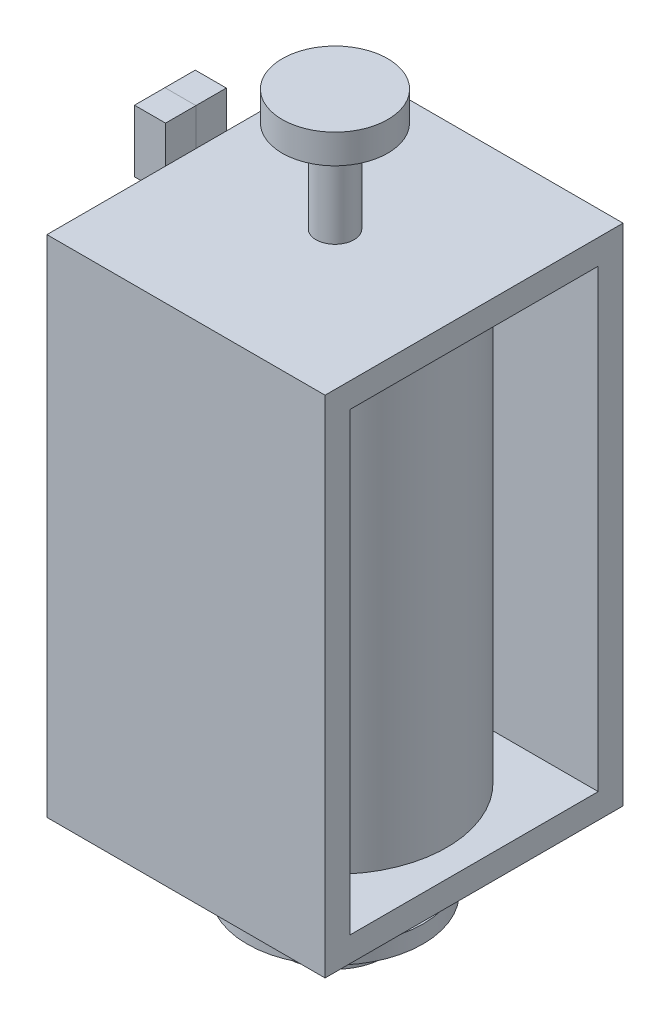
SolidWorks part; units mm, degrees
ref_plane "Front Plane" through (0, 0, 0) normal (0, 0, 1) x (1, 0, 0)
ref_plane "Top Plane" through (0, 0, 0) normal (0, 1, 0) x (1, 0, 0)
ref_plane "Right Plane" through (0, 0, 0) normal (1, 0, 0) x (0, 0, -1)
sketch "Sketch3" plane through (0, 0, 0) normal (1, 0, 0) x (0, 0, -1)
  line L1 (6.096, -10.3251) -> (-6.096, -10.3251)
  line L2 (6.096, -10.3251) -> (6.096, 10.3251)
  line L3 (6.096, 10.3251) -> (-6.096, 10.3251)
  line L4 (-6.096, -10.3251) -> (-6.096, 10.3251)
  line L5 (6.096, -10.3251) -> (-6.096, 10.3251) construction
  line L6 (6.096, 10.3251) -> (-6.096, -10.3251) construction
  line L7 (5.08, -9.3091) -> (-5.08, -9.3091)
  line L8 (5.08, -9.3091) -> (5.08, 9.3091)
  line L9 (5.08, 9.3091) -> (-5.08, 9.3091)
  line L10 (-5.08, -9.3091) -> (-5.08, 9.3091)
  line L11 (5.08, -9.3091) -> (-5.08, 9.3091) construction
  line L12 (5.08, 9.3091) -> (-5.08, -9.3091) construction
  point P0 (0, 0)
  point P6 (0, 0)
  dimension "D1" = 20.6502
  dimension "D2" = 12.192
  dimension "D3" = 1.016
  dimension "D4" = 1.016
extrude "Boss-Extrude3" add sketch "Sketch3" along normal mid plane 11.3792 separate body
sketch "Sketch2" plane through (0, 0, 0) normal (0, 1, 0) x (1, 0, 0)
  circle A0 centre (0, 0) radius 4.572
  dimension "D1" = 9.144
extrude "Boss-Extrude2" add sketch "Sketch2" along normal mid plane 18.796
sketch "Sketch4" plane through (0, 10.3251, 0) normal (0, 1, 0) x (1, 0, 0)
  circle A0 centre (0, 0) radius 0.7747
  circle A1 centre (0, 0) radius 2.159
  dimension "D1" = 4.318
  dimension "D2" = 1.5494
extrude "Boss-Extrude4" add sketch "Sketch4" along normal blind 3.7592 separate body contours A0 region at (0, 10.3251, 0)
sketch "Sketch5" plane through (0, -10.3251, 0) normal (0, -1, 0) x (1, 0, 0)
  circle A0 centre (0, 0) radius 2.0066
  dimension "D1" = 4.0132
extrude "Boss-Extrude5" add sketch "Sketch5" along normal blind 4.1656
ref_plane "Plane1" through (0, -12.5095, 0) normal (0, -1, 0) x (-1, 0, 0)
sketch "Sketch6" plane through (0, -12.5095, 0) normal (0, -1, 0) x (1, 0, 0)
  line L0 (-2.667, -2.4093) -> (-1.489, -1.3451)
  line L1 (1.489, -1.3451) -> (2.667, -2.4093)
  line L2 (-3.5689, -1.3451) -> (3.5689, -1.3451) construction
  line L3 (-5.0182, -2.4093) -> (5.0182, -2.4093) construction
  arc A0 (2.667, -2.4093) -> (-2.667, -2.4093) centre (0, 0) ccw
  circle A1 centre (0, 0) radius 2.0066 construction
  circle A2 centre (0, 0) radius 2.0066 construction
  arc A3 (1.489, -1.3451) -> (-1.489, -1.3451) centre (0, 0) ccw
  point P13 (0, -1.3451)
  point P17 (0, -2.4093)
  dimension "D1" = 7.1882
  dimension "D3" = 5.334
extrude "Boss-Extrude11" add sketch "Sketch6" along normal blind 0.7112
sketch "Sketch7" plane through (-5.6896, 0, 0) normal (-1, 0, 0) x (0, 0, 1)
  line L0 (-1.2429, 11.8491) -> (-1.2429, 9.3091)
  line L1 (-5.08, 9.3091) -> (5.08, 9.3091) construction
  line L2 (-1.2429, 9.3091) -> (0, 9.3091)
  line L3 (0, 9.3091) -> (0, 11.8491)
  line L4 (0, 11.8491) -> (-1.2429, 11.8491)
  line L5 (0, 11.8491) -> (1.2429, 11.8491)
  line L6 (1.2429, 11.8491) -> (1.2429, 9.3091)
  line L7 (1.2429, 9.3091) -> (0, 9.3091)
  line L8 (-5.08, 9.3091) -> (5.08, 9.3091) construction
  point P8 (0, 9.3091)
  line M10 (6.096, 10.3251) -> (-6.096, 10.3251)
  line M16 (-5.08, 9.3091) -> (5.08, 9.3091)
  dimension "D1" = 2.4857
  dimension "D2" = 2.54
extrude "Boss-Extrude12" add sketch "Sketch7" along normal blind 1.27 separate body contours L3 L4 L0 M10 | L3 L0 M16 M10 region at (-5.6896, 11.0871, -0.6214) region at (-5.6896, 9.8171, -0.6214)
extrude "Boss-Extrude13" add sketch "Sketch7<3>" along normal blind 1.27 separate body contours L6 L5 L3 M10 | L6 L3 M10 M16 region at (-5.6896, 11.0871, 0.6214) region at (-5.6896, 9.8171, 0.6214)
sketch "Sketch7<3>" plane through (-5.6896, 0, 0) normal (-1, 0, 0) x (0, 0, 1) same geometry as "Sketch7"
sketch "Sketch8" plane through (0, 14.0843, 0) normal (0, 1, 0) x (1, 0, 0)
  circle A0 centre (0, 0) radius 0.7747 construction
  circle A1 centre (0, 0) radius 2.159 construction
  circle A2 centre (0, 0) radius 0.7747
  circle A3 centre (0, 0) radius 2.159
  circle M1 centre (0, 0) radius 0.7747
extrude "Boss-Extrude14" add sketch "Sketch8" along normal blind 1.1938 separate body contours M1 | A3 M1 region at (0, 14.0843, 0) region at (-2.0979, 14.0843, 0)
